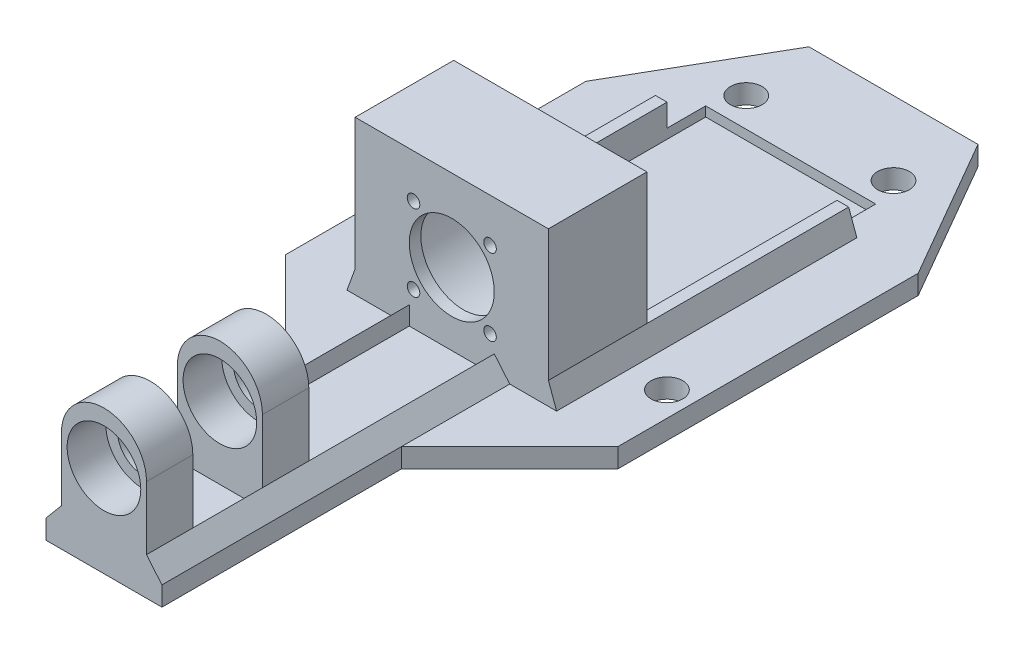
SolidWorks part; units mm, degrees
other "Marquage1"
sketch "Esquisse29" plane through (68, 42.3, 115.5) normal (0.0061, 0.608, 0.7939) x (1, 0, -0.0077)
ref_plane "Plan de face" through (0, 0, 0) normal (0, 0, 1) x (1, 0, 0)
ref_plane "Plan de dessus" through (0, 0, 0) normal (0, 1, 0) x (1, 0, 0)
ref_plane "Plan de droite" through (0, 0, 0) normal (1, 0, 0) x (0, 0, -1)
sketch "Esquisse1" plane through (0, 0, 0) normal (0, 0, 1) x (1, 0, 0)
  line L1 (0, 0) -> (50, 0)
  line L2 (0, 0) -> (0, 42.3)
  line L3 (0, 42.3) -> (50, 42.3)
  line L4 (50, 0) -> (50, 42.3)
  dimension "D1" = 42.3
  dimension "D2" = 50
extrude "Boss.-Extru.1" add sketch "Esquisse1" along normal blind 25.5
sketch "Esquisse4" plane through (0, 0, 0) normal (0, 0, 1) x (1, 0, 0)
  line L1 (0, 0) -> (50, 0) construction
  line L5 (25, 42.3) -> (25, 0) construction
  line L6 (50, 42.3) -> (0, 42.3) construction
  circle A0 centre (25, 21.15) radius 18.1
  point P3 (25, 21.15)
  dimension "D1" = 36.2
extrude "Enlèv. mat.-Extru.3" cut sketch "Esquisse4" along normal offset from surface (22.5 mm away) 3 up to face at (25, 21.15, 25.5)
sketch "Esquisse5" plane through (37, 0, 25.5) normal (0, 0, -1) x (-1, 0, 0)
  circle A0 centre (12, 21.15) radius 11
  dimension "D1" = 22
extrude "Enlèv. mat.-Extru.4" cut sketch "Esquisse5" against normal through all and the other way through all
sketch "Esquisse6" plane through (0, 0, 25.5) normal (0, 0, -1) x (-1, 0, 0)
  line L0 (-25, 21.15) -> (-34.8995, 31.0495) construction
  line L2 (-36, 21.15) -> (-25, 21.15) construction
  circle A1 centre (-25, 21.15) radius 11 construction
  circle A2 centre (-34.8995, 31.0495) radius 1.625
  circle A3 centre (-25, 21.15) radius 14 construction
  circle A4 centre (-15.1005, 31.0495) radius 1.625
  circle A5 centre (-25, 21.15) radius 14 construction
  circle A6 centre (-15.1005, 11.2505) radius 1.625
  circle A7 centre (-25, 21.15) radius 14 construction
  circle A8 centre (-34.8995, 11.2505) radius 1.625
  circle A9 centre (-25, 21.15) radius 14 construction
  point P9 (-25, 21.15)
  point P17 (-32.7782, 28.9282)
  point P22 (-25, 21.15)
  dimension "D1" = 28
  dimension "D2" = 3.25
  dimension "D3" = 45
  dimension "D4" = 4
extrude "Enlèv. mat.-Extru.5" cut sketch "Esquisse6" along normal blind 10
ref_plane "Plan1" through (0, 21.15, 0) normal (0, -1, 0) x (-1, 0, 0)
ref_plane "Plan2" through (25, 0, 0) normal (-1, 0, 0) x (0, 0, 1)
sketch "Esquisse7" plane through (0, 0, 25.5) normal (0, 0, 1) x (1, 0, 0)
  line L0 (50, 0) -> (68, 0)
  line L2 (50, 0) -> (50, 42.3) construction
  line L4 (50, 2.5) -> (68, 2.5) construction
  line L8 (68, 0) -> (68, 2.5)
  line L9 (68, 2.5) -> (52.1229, 2.5)
  line L11 (50, 8.3325) -> (50, 0)
  line L12 (25, 14.025) -> (25, -14.025) construction
  line L17 (50, 8.3325) -> (52.1229, 2.5)
  line L18 (-18, 0) -> (-18, 2.5)
  line L19 (0, 0) -> (-18, 0)
  line L20 (-18, 2.5) -> (-2.1229, 2.5)
  line L21 (0, 8.3325) -> (-2.1229, 2.5)
  line L22 (0, 8.3325) -> (0, 0)
  dimension "D1" = 18
  dimension "D2" = 2.5
  dimension "D3" = 20
  dimension "D4" = 5.8325
extrude "Boss.-Extru.2" add sketch "Esquisse7" against normal blind 77.7
sketch "Esquisse16" plane through (0, 0, 0) normal (0, 0, -1) x (-1, 0, 0)
  line L2 (0, 0) -> (-50, 0) construction
  line L3 (0, 8.3325) -> (-3, 8.3325)
  line L4 (-3, 8.3325) -> (-3, 0)
  line L5 (-25, 41.9209) -> (-25, -9.8537) construction
  line L6 (-50, 0) -> (-50, 8.3325)
  line L7 (-25, -14.025) -> (-25, 14.025) construction
  line L10 (-3, 0) -> (0, 0)
  line L11 (0, 0) -> (0, 8.3325)
  line L12 (-47, 0) -> (-50, 0)
  line L13 (-47, 8.3325) -> (-47, 0)
  line L14 (-50, 8.3325) -> (-47, 8.3325)
  dimension "D1" = 44
extrude "Boss.-Extru.4" add sketch "Esquisse16" along normal up to surface (52.2 mm away) up to face at (57.6246, 2.6665, -52.2)
sketch "Esquisse17" plane through (0, 0, 25.5) normal (0, 0, 1) x (1, 0, 0)
  line L1 (-18, 0) -> (68, 0)
  line L2 (-18, 0) -> (-18, -2.5)
  line L3 (-18, -2.5) -> (68, -2.5)
  line L4 (68, 0) -> (68, -2.5)
  dimension "D1" = 2.5
extrude "Boss.-Extru.5" add sketch "Esquisse17" against normal up to surface (77.7 mm away) up to face at (-5.3538, 3.6108, -52.2)
sketch "Esquisse20" plane through (0, -2.5, 0) normal (0, -1, 0) x (1, 0, 0)
  line L0 (-18, 25.5) -> (10, 53.5)
  line L1 (10, 53.5) -> (10, 115.5)
  line L2 (10, 115.5) -> (40, 115.5)
  line L3 (40, 115.5) -> (40, 53.5)
  line L4 (40, 53.5) -> (68, 25.5)
  line L5 (25, 25.5) -> (25, 57.1166) construction
  line L8 (25, 14.025) -> (25, -14.025) construction
  line L9 (-18, 25.5) -> (68, 25.5) construction
  line L10 (-18, 25.5) -> (68, 25.5)
  dimension "D1" = 90
  dimension "D2" = 45
  dimension "D3" = 30
extrude "Boss.-Extru.7" add sketch "Esquisse20" against normal blind 5
sketch "Esquisse21" plane through (0, 0, 115.5) normal (0, 0, 1) x (1, 0, 0)
  line L0 (10, 2.5) -> (14, 7.267)
  line L1 (14, 7.267) -> (14, 23.65)
  line L2 (40, 2.5) -> (10, 2.5)
  line L3 (36, 23.65) -> (36, 7.267)
  line L4 (36, 7.267) -> (40, 2.5)
  line L5 (25, 0) -> (25, 46.5044) construction
  line L7 (40, 2.5) -> (10, 2.5) construction
  arc A0 (36, 23.65) -> (14, 23.65) centre (25, 23.65) ccw
  point P11 (25, 2.5)
  dimension "D2" = 11
  dimension "D1" = 21.15
  dimension "D3" = 50
extrude "Boss.-Extru.8" add sketch "Esquisse21" against normal blind 12
sketch "Esquisse22" plane through (0, 0, 115.5) normal (0, 0, 1) x (1, 0, 0)
  circle A0 centre (25, 21.15) radius 9.525
  dimension "D1" = 19.05
extrude "Enlèv. mat.-Extru.6" cut sketch "Esquisse22" against normal blind 10
ref_axis "Axe1" through (25, 2.5, 103.5) along (0, 0, -1)
pattern_linear "Répétition linéaire2" count 2 spacing 30 along (0, 0, -1) of "Boss.-Extru.8", "Enlèv. mat.-Extru.6"
sketch "Esquisse23" plane through (0, 0, 105.5) normal (0, 0, 1) x (1, 0, 0)
  circle A0 centre (25, 21.15) radius 6.5
  dimension "D1" = 13
extrude "Enlèv. mat.-Extru.7" cut sketch "Esquisse23" against normal through all
sketch "Esquisse26" plane through (0, -2.5, 0) normal (0, -1, 0) x (1, 0, 0)
  line L0 (-18, -52.2) -> (3.131, -88.8)
  line L1 (3.131, -88.8) -> (46.869, -88.8)
  line L2 (46.869, -88.8) -> (68, -52.2)
  line L3 (68, -52.2) -> (-18, -52.2)
  line L4 (25, 0) -> (25, -112.6897) construction
  line L6 (25, 103.5) -> (25, 25.5) construction
  dimension "D1" = 36.6
  dimension "D2" = 60
extrude "Boss.-Extru.9" add sketch "Esquisse26" against normal up to surface (5 mm away) up to face at (25, 2.5, 12.2667)
sketch "Esquisse27" plane through (0, 0, -52.2) normal (0, 0, 1) x (1, 0, 0)
  line L0 (47, 0) -> (3, 0) construction
  line L1 (3, 2.5) -> (47, 2.5)
  line L2 (3, 2.5) -> (3, 0)
  line L3 (3, 0) -> (47, 0)
  line L4 (47, 2.5) -> (47, 0)
extrude "Enlèv. mat.-Extru.9" cut sketch "Esquisse27" against normal blind 10
sketch "Esquisse24" plane through (0, 2.5, 0) normal (0, 1, 0) x (1, 0, 0)
  line L0 (-11.6229, -6.45) -> (61.6229, -6.45) construction
  line L1 (53.1229, 9.2568) -> (53.1229, -15.1268) construction
  line L4 (5.95, 69.75) -> (44.05, 69.75) construction
  line L5 (25, -11.3965) -> (25, 17.2813) construction
  line L6 (3, 52.2) -> (-2.1229, 52.2) construction
  line L7 (25, 14.025) -> (25, -14.025) construction
  line L8 (-2.1229, -25.5) -> (52.1229, -25.5) construction
  line L10 (52.1229, 52.2) -> (52.1229, -25.5) construction
  circle A0 centre (61.6229, -6.45) radius 4.1
  circle A1 centre (-11.6229, -6.45) radius 4.1
  circle A4 centre (5.95, 69.75) radius 4.1
  circle A5 centre (44.05, 69.75) radius 4.1
  circle A8 centre (61.6229, -6.45) radius 8.5 construction
  point P21 (25, 69.75)
  dimension "D1" = 8.2
  dimension "D5" = 17
  dimension "D6" = 1
  dimension "D2" = 19.05
  dimension "D4" = 17.55
  dimension "D3" = 38.1
extrude "Enlèv. mat.-Extru.8" cut sketch "Esquisse24" against normal through all
sketch "Esquisse28" plane through (0, 0, 115.5) normal (0, 0, 1) x (1, 0, 0)
  line L0 (14, 7.267) -> (14, 2.5)
  line L5 (10, 2.5) -> (14, 2.5)
  line L12 (10, 2.5) -> (10, -2.5) construction
  line L13 (14, 7.267) -> (10, 2.5) construction
  line L14 (36, 7.267) -> (36, 2.5)
  line L15 (40, 2.5) -> (36, 7.267) construction
  line L16 (36, 2.5) -> (40, 2.5)
  line L17 (10, 2.5) -> (-18, 2.5) construction
  line L18 (-2.1229, 2.5) -> (52.1229, 2.5) construction
  line L19 (14, 7.267) -> (10, 2.5)
  line L20 (40, 2.5) -> (36, 7.267)
extrude "Boss.-Extru.10" add sketch "Esquisse28" against normal up to surface (90 mm away) up to face at (33.2745, 11.2505, 25.5)
